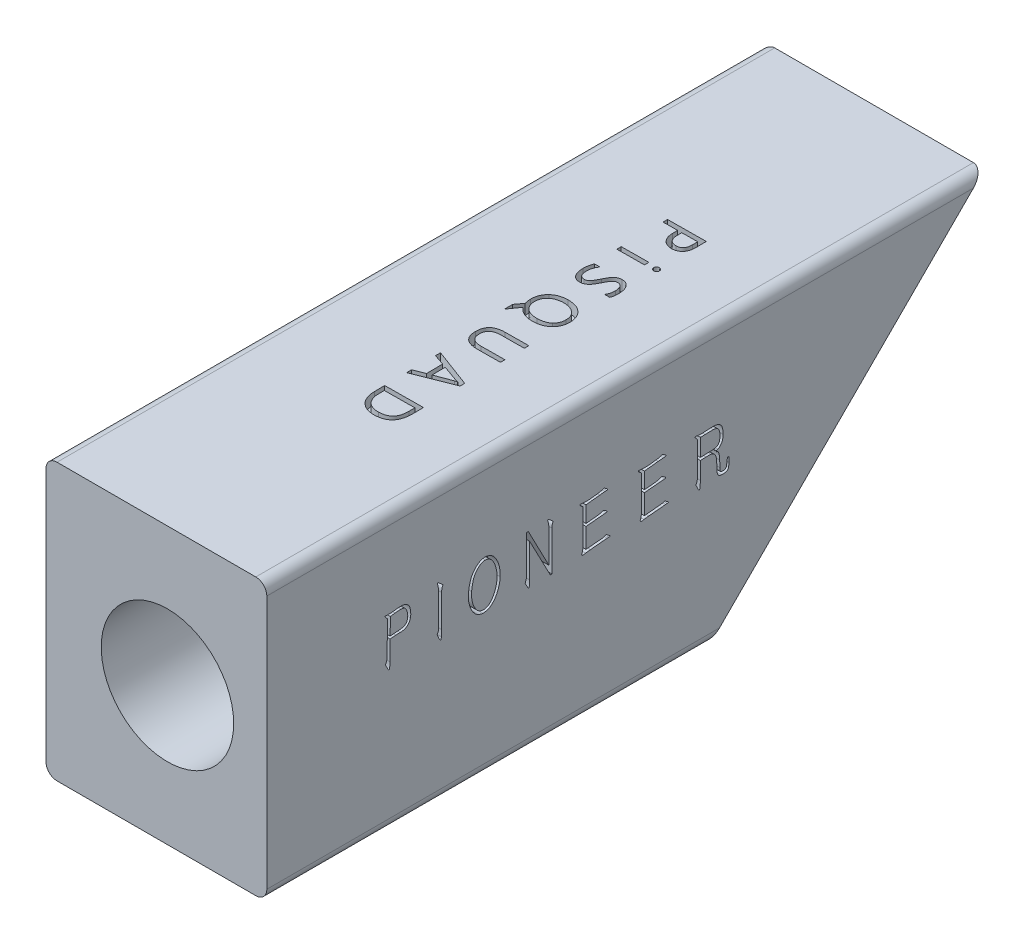
SolidWorks part; units mm, degrees
ref_plane "前视基准面" through (0, 0, 0) normal (0, 0, 1) x (1, 0, 0)
ref_plane "上视基准面" through (0, 0, 0) normal (0, 1, 0) x (1, 0, 0)
ref_plane "右视基准面" through (0, 0, 0) normal (1, 0, 0) x (0, 0, -1)
other "Configuration Table"
sketch "Sketch1" plane through (0, 0, 0) normal (1, 0, 0) x (0, 0, -1)
  line L0 (20, -12.5) -> (45, 12.5)
  line L1 (-20, -12.5) -> (20, -12.5)
  line L2 (-20, -12.5) -> (-20, 12.5)
  line L3 (-20, 12.5) -> (20, 12.5)
  line L4 (20, -12.5) -> (20, 12.5)
  line L5 (-20, -12.5) -> (20, 12.5) construction
  line L6 (-20, 12.5) -> (20, -12.5) construction
  line L7 (20, 12.5) -> (45, 12.5)
  point P0 (0, 0)
  dimension "D1" = 25
  dimension "D2" = 40
  dimension "D3" = 45
extrude "Boss-Extrude1" add sketch "Sketch1" along normal blind 20 contours L7 L4 L0 | L1 L4 L3 L2 region at (0, 4.1667, -28.3333) region at (0, 0, 0)
sketch "Sketch2" plane through (0, 0, 0) normal (0, 0, 1) x (1, 0, 0)
  line L0 (10, 12.5) -> (10, -12.5) construction
  line L1 (20, 12.5) -> (0, 12.5) construction
  line L2 (20, -12.5) -> (0, -12.5) construction
  line L3 (0, 0) -> (20, 0) construction
  line L4 (20, -12.5) -> (20, 12.5) construction
  circle A0 centre (11, 0) radius 6
  dimension "D1" = 9
extrude "Cut-Extrude1" cut sketch "Sketch2" against normal blind 67 and the other way blind 43
fillet "Fillet1" radius 1 4 edges at (0, 12.5, -12.5) (0, -12.5, 0) (20, -12.5, 0) (20, 12.5, -12.5)
sketch "Sketch4" plane through (0, 0, 0) normal (-1, 0, 0) x (0, 0, 1)
  circle A0 centre (0, 0) radius 11
extrude "Cut-Extrude2" cut sketch "Sketch4" against normal blind 2
sketch "Sketch5" plane through (0, 12.5, 0) normal (0, 1, 0) x (1, 0, 0)
  line L0 (9.4482, 45) -> (10, -20) construction
  line L1 (19, 45) -> (1, 45) construction
  line L2 (19, -20) -> (1, -20) construction
  text T0 "PiSQUAD" font "Segoe UI" height 3.5
extrude "Cut-Extrude3" cut sketch "Sketch5" against normal blind 1
sketch "Sketch6" plane through (20, 0, 0) normal (1, 0, 0) x (0, 0, -1)
  line L0 (-20, 0) -> (32.5, 0) construction
  line L1 (-20, -11.5) -> (-20, 11.5) construction
  line L2 (21, -11.5) -> (44, 11.5) construction
  text T0 "PIONEER" font "汉仪长仿宋体" height in points 18
extrude "Cut-Extrude4" cut sketch "Sketch6" against normal blind 1
